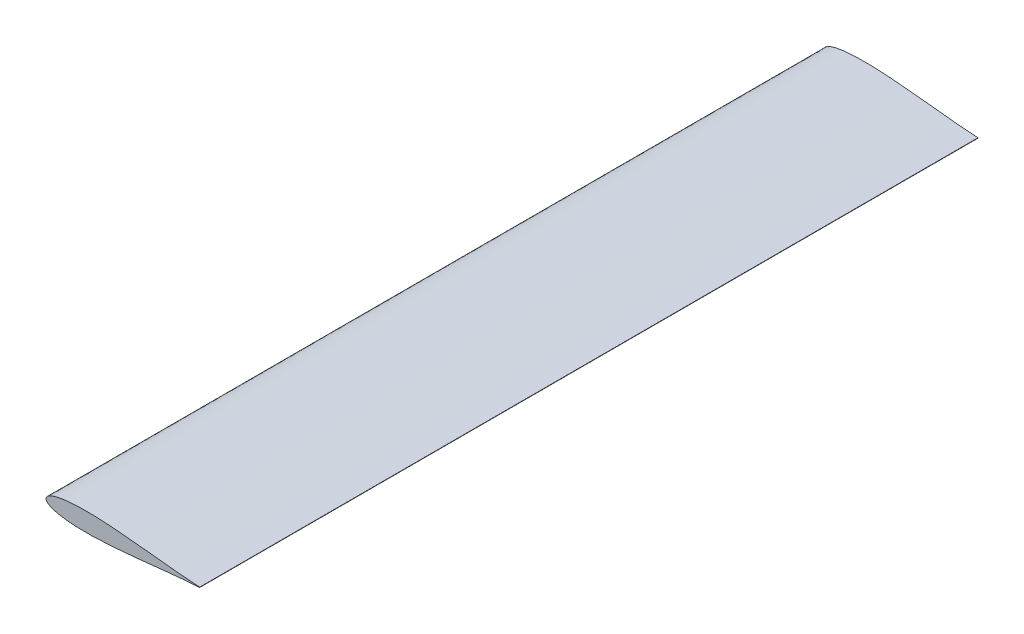
SolidWorks part; units mm, degrees
other "Markup1"
sketch "Sketch3" plane through (-0.0553, -7.355, 609.6) normal (0, 0, 1) x (1, 0, 0)
ref_plane "Front Plane" through (0, 0, 0) normal (0, 0, 1) x (1, 0, 0)
ref_plane "Top Plane" through (0, 0, 0) normal (0, 1, 0) x (1, 0, 0)
ref_plane "Right Plane" through (0, 0, 0) normal (1, 0, 0) x (0, 0, -1)
curve "Curve1"
  spline degree 3 poles (25.3337, -0.0003, 0) (25.4166, 0, 0) (25.3337, 0.0003, 0) (25.2654, 0.0018, 0) (25.098, 0.0055, 0) (24.8899, 0.0127, 0) (24.614, 0.0243, 0) (24.2833, 0.0411, 0) (23.8951, 0.064, 0) (23.4526, 0.0935, 0) (22.9577, 0.1302, 0) (22.4128, 0.1742, 0) (21.8206, 0.2257, 0) (21.184, 0.2845, 0) (20.5061, 0.3502, 0) (19.7901, 0.4224, 0) (19.0396, 0.5004, 0) (18.2582, 0.5832, 0) (17.4498, 0.6697, 0) (16.6182, 0.7589, 0) (15.7675, 0.8494, 0) (14.9019, 0.9396, 0) (14.0255, 1.0282, 0) (13.1427, 1.1135, 0) (12.2578, 1.1941, 0) (11.3749, 1.2683, 0) (10.4986, 1.3345, 0) (9.6329, 1.3915, 0) (8.7821, 1.4377, 0) (7.9504, 1.4721, 0) (7.1418, 1.4935, 0) (6.3603, 1.501, 0) (5.6096, 1.4941, 0) (4.8934, 1.4721, 0) (4.2152, 1.4349, 0) (3.5783, 1.3824, 0) (2.9857, 1.3149, 0) (2.4403, 1.233, 0) (1.9447, 1.1371, 0) (1.5013, 1.0283, 0) (1.1121, 0.9078, 0) (0.7787, 0.7769, 0) (0.5025, 0.6369, 0) (0.2843, 0.4891, 0) (0.1244, 0.334, 0) (0.024, 0.1711, 0) (-0.0113, 0, 0) (0.024, -0.1711, 0) (0.1244, -0.334, 0) (0.2843, -0.4891, 0) (0.5025, -0.6369, 0) (0.7787, -0.7769, 0) (1.1121, -0.9078, 0) (1.5013, -1.0283, 0) (1.9447, -1.1371, 0) (2.4403, -1.233, 0) (2.9857, -1.3149, 0) (3.5783, -1.3824, 0) (4.2152, -1.4349, 0) (4.8934, -1.4721, 0) (5.6096, -1.4941, 0) (6.3603, -1.501, 0) (7.1418, -1.4935, 0) (7.9504, -1.4721, 0) (8.7821, -1.4377, 0) (9.6329, -1.3915, 0) (10.4986, -1.3345, 0) (11.3749, -1.2683, 0) (12.2578, -1.1941, 0) (13.1427, -1.1135, 0) (14.0255, -1.0282, 0) (14.9019, -0.9396, 0) (15.7675, -0.8494, 0) (16.6182, -0.7589, 0) (17.4498, -0.6697, 0) (18.2582, -0.5832, 0) (19.0396, -0.5004, 0) (19.7901, -0.4224, 0) (20.5061, -0.3502, 0) (21.184, -0.2845, 0) (21.8206, -0.2257, 0) (22.4128, -0.1742, 0) (22.9577, -0.1302, 0) (23.4526, -0.0935, 0) (23.8951, -0.064, 0) (24.2833, -0.0411, 0) (24.614, -0.0243, 0) (24.8899, -0.0127, 0) (25.098, -0.0055, 0) (25.2654, -0.0018, 0) (25.3337, -0.0003, 0) (25.4166, 0, 0) (25.3337, 0.0003, 0) knots -0.005355 -0.002385 -0.000597 0 0.000597 0.002385 0.005355 0.009495 0.014784 0.021198 0.028708 0.037278 0.046868 0.05743 0.068917 0.081271 0.094432 0.108338 0.122919 0.138103 0.153815 0.169978 0.186509 0.203327 0.220349 0.237488 0.25466 0.271779 0.288763 0.305527 0.32199 0.338073 0.353702 0.368803 0.383306 0.397149 0.410269 0.422614 0.434133 0.444783 0.454527 0.463337 0.471194 0.478092 0.484042 0.489082 0.493295 0.496842 0.5 0.503158 0.506705 0.510918 0.515958 0.521908 0.528806 0.536663 0.545473 0.555218 0.565867 0.577386 0.589731 0.602851 0.616694 0.631197 0.646298 0.661927 0.67801 0.694473 0.711237 0.728221 0.74534 0.762512 0.779651 0.796673 0.813491 0.830023 0.846185 0.861897 0.877081 0.891662 0.905568 0.918729 0.931083 0.94257 0.953133 0.962722 0.971292 0.978802 0.985216 0.990505 0.994645 0.997615 0.999403 1 1.000597 1.002385 1.005355 periodic
sketch "Sketch2" plane through (0, 0, 0) normal (0, 0, 1) x (1, 0, 0)
  line L0 (0, 0) -> (25.4, 0) construction
  line L1 (0, 0) -> (124.46, 0) construction
  line L2 (120.381, 0.1319) -> (120.381, -0.1319)
  line L3 (62.23, 0) -> (62.23, 5.6527) construction
  spline S0 degree 3 poles (25.3337, -0.0003) (25.4166, 0) (25.3337, 0.0003) (25.2654, 0.0018) (25.098, 0.0055) (24.8899, 0.0127) (24.614, 0.0243) (24.2833, 0.0411) (23.8951, 0.064) (23.4526, 0.0935) (22.9577, 0.1302) (22.4128, 0.1742) (21.8206, 0.2257) (21.184, 0.2845) (20.5061, 0.3502) (19.7901, 0.4224) (19.0396, 0.5004) (18.2582, 0.5832) (17.4498, 0.6697) (16.6182, 0.7589) (15.7675, 0.8494) (14.9019, 0.9396) (14.0255, 1.0282) (13.1427, 1.1135) (12.2578, 1.1941) (11.3749, 1.2683) (10.4986, 1.3345) (9.6329, 1.3915) (8.7821, 1.4377) (7.9504, 1.4721) (7.1418, 1.4935) (6.3603, 1.501) (5.6096, 1.4941) (4.8934, 1.4721) (4.2152, 1.4349) (3.5783, 1.3824) (2.9857, 1.3149) (2.4403, 1.233) (1.9447, 1.1371) (1.5013, 1.0283) (1.1121, 0.9078) (0.7787, 0.7769) (0.5025, 0.6369) (0.2843, 0.4891) (0.1244, 0.334) (0.024, 0.1711) (-0.0113, 0) (0.024, -0.1711) (0.1244, -0.334) (0.2843, -0.4891) (0.5025, -0.6369) (0.7787, -0.7769) (1.1121, -0.9078) (1.5013, -1.0283) (1.9447, -1.1371) (2.4403, -1.233) (2.9857, -1.3149) (3.5783, -1.3824) (4.2152, -1.4349) (4.8934, -1.4721) (5.6096, -1.4941) (6.3603, -1.501) (7.1418, -1.4935) (7.9504, -1.4721) (8.7821, -1.4377) (9.6329, -1.3915) (10.4986, -1.3345) (11.3749, -1.2683) (12.2578, -1.1941) (13.1427, -1.1135) (14.0255, -1.0282) (14.9019, -0.9396) (15.7675, -0.8494) (16.6182, -0.7589) (17.4498, -0.6697) (18.2582, -0.5832) (19.0396, -0.5004) (19.7901, -0.4224) (20.5061, -0.3502) (21.184, -0.2845) (21.8206, -0.2257) (22.4128, -0.1742) (22.9577, -0.1302) (23.4526, -0.0935) (23.8951, -0.064) (24.2833, -0.0411) (24.614, -0.0243) (24.8899, -0.0127) (25.098, -0.0055) (25.2654, -0.0018) (25.3337, -0.0003) (25.4166, 0) (25.3337, 0.0003) knots -0.005355 -0.002385 -0.000597 0 0.000597 0.002385 0.005355 0.009495 0.014784 0.021198 0.028708 0.037278 0.046868 0.05743 0.068917 0.081271 0.094432 0.108338 0.122919 0.138103 0.153815 0.169978 0.186509 0.203327 0.220349 0.237488 0.25466 0.271779 0.288763 0.305527 0.32199 0.338073 0.353702 0.368803 0.383306 0.397149 0.410269 0.422614 0.434133 0.444783 0.454527 0.463337 0.471194 0.478092 0.484042 0.489082 0.493295 0.496842 0.5 0.503158 0.506705 0.510918 0.515958 0.521908 0.528806 0.536663 0.545473 0.555218 0.565867 0.577386 0.589731 0.602851 0.616694 0.631197 0.646298 0.661927 0.67801 0.694473 0.711237 0.728221 0.74534 0.762512 0.779651 0.796673 0.813491 0.830023 0.846185 0.861897 0.877081 0.891662 0.905568 0.918729 0.931083 0.94257 0.953133 0.962722 0.971292 0.978802 0.985216 0.990505 0.994645 0.997615 0.999403 1 1.000597 1.002385 1.005355 only from (25.4, 0) to (25.4, 0) construction
  spline S1 degree 3 poles (25.3337, -0.0003) (25.4166, 0) (25.3337, 0.0003) (25.2654, 0.0018) (25.098, 0.0055) (24.8899, 0.0127) (24.614, 0.0243) (24.2833, 0.0411) (23.8951, 0.064) (23.4526, 0.0935) (22.9577, 0.1302) (22.4128, 0.1742) (21.8206, 0.2257) (21.184, 0.2845) (20.5061, 0.3502) (19.7901, 0.4224) (19.0396, 0.5004) (18.2582, 0.5832) (17.4498, 0.6697) (16.6182, 0.7589) (15.7675, 0.8494) (14.9019, 0.9396) (14.0255, 1.0282) (13.1427, 1.1135) (12.2578, 1.1941) (11.3749, 1.2683) (10.4986, 1.3345) (9.6329, 1.3915) (8.7821, 1.4377) (7.9504, 1.4721) (7.1418, 1.4935) (6.3603, 1.501) (5.6096, 1.4941) (4.8934, 1.4721) (4.2152, 1.4349) (3.5783, 1.3824) (2.9857, 1.3149) (2.4403, 1.233) (1.9447, 1.1371) (1.5013, 1.0283) (1.1121, 0.9078) (0.7787, 0.7769) (0.5025, 0.6369) (0.2843, 0.4891) (0.1244, 0.334) (0.024, 0.1711) (-0.0113, 0) (0.024, -0.1711) (0.1244, -0.334) (0.2843, -0.4891) (0.5025, -0.6369) (0.7787, -0.7769) (1.1121, -0.9078) (1.5013, -1.0283) (1.9447, -1.1371) (2.4403, -1.233) (2.9857, -1.3149) (3.5783, -1.3824) (4.2152, -1.4349) (4.8934, -1.4721) (5.6096, -1.4941) (6.3603, -1.501) (7.1418, -1.4935) (7.9504, -1.4721) (8.7821, -1.4377) (9.6329, -1.3915) (10.4986, -1.3345) (11.3749, -1.2683) (12.2578, -1.1941) (13.1427, -1.1135) (14.0255, -1.0282) (14.9019, -0.9396) (15.7675, -0.8494) (16.6182, -0.7589) (17.4498, -0.6697) (18.2582, -0.5832) (19.0396, -0.5004) (19.7901, -0.4224) (20.5061, -0.3502) (21.184, -0.2845) (21.8206, -0.2257) (22.4128, -0.1742) (22.9577, -0.1302) (23.4526, -0.0935) (23.8951, -0.064) (24.2833, -0.0411) (24.614, -0.0243) (24.8899, -0.0127) (25.098, -0.0055) (25.2654, -0.0018) (25.3337, -0.0003) (25.4166, 0) (25.3337, 0.0003) knots -0.005355 -0.002385 -0.000597 0 0.000597 0.002385 0.005355 0.009495 0.014784 0.021198 0.028708 0.037278 0.046868 0.05743 0.068917 0.081271 0.094432 0.108338 0.122919 0.138103 0.153815 0.169978 0.186509 0.203327 0.220349 0.237488 0.25466 0.271779 0.288763 0.305527 0.32199 0.338073 0.353702 0.368803 0.383306 0.397149 0.410269 0.422614 0.434133 0.444783 0.454527 0.463337 0.471194 0.478092 0.484042 0.489082 0.493295 0.496842 0.5 0.503158 0.506705 0.510918 0.515958 0.521908 0.528806 0.536663 0.545473 0.555218 0.565867 0.577386 0.589731 0.602851 0.616694 0.631197 0.646298 0.661927 0.67801 0.694473 0.711237 0.728221 0.74534 0.762512 0.779651 0.796673 0.813491 0.830023 0.846185 0.861897 0.877081 0.891662 0.905568 0.918729 0.931083 0.94257 0.953133 0.962722 0.971292 0.978802 0.985216 0.990505 0.994645 0.997615 0.999403 1 1.000597 1.002385 1.005355 only from (25.4, 0) to (25.4, 0) construction
  spline S2 degree 3 poles (120.381, 0.1319) (119.9463, 0.1527) (118.8798, 0.2078) (117.0858, 0.3137) (114.9178, 0.4584) (112.4927, 0.6382) (109.8228, 0.8537) (106.9211, 1.106) (103.8017, 1.394) (100.4797, 1.7159) (96.9715, 2.0698) (93.294, 2.4518) (89.4653, 2.8575) (85.5038, 3.2818) (81.4291, 3.7187) (77.2608, 4.162) (73.0193, 4.6041) (68.7252, 5.0383) (64.3994, 5.4564) (60.0631, 5.8512) (55.7372, 6.2145) (51.4429, 6.5392) (47.2011, 6.8181) (43.0324, 7.0448) (38.9571, 7.2131) (34.9951, 7.3181) (31.1655, 7.355) (27.4872, 7.3209) (23.9779, 7.2133) (20.6546, 7.0309) (17.5336, 6.7739) (14.6298, 6.4432) (11.9574, 6.0415) (9.5291, 5.5718) (7.3563, 5.0389) (5.4492, 4.4484) (3.8158, 3.8067) (2.4624, 3.1207) (1.3928, 2.3964) (0.6096, 1.6368) (0.1174, 0.8384) (-0.0553, 0) (0.1174, -0.8384) (0.6096, -1.6368) (1.3928, -2.3964) (2.4624, -3.1207) (3.8158, -3.8067) (5.4492, -4.4484) (7.3563, -5.0389) (9.5291, -5.5718) (11.9574, -6.0415) (14.6299, -6.4433) (17.5336, -6.7739) (20.6546, -7.0309) (23.9779, -7.2133) (27.4872, -7.3209) (31.1655, -7.355) (34.9951, -7.3181) (38.9571, -7.2131) (43.0324, -7.0448) (47.2011, -6.8181) (51.4429, -6.5392) (55.7372, -6.2145) (60.0631, -5.8512) (64.3994, -5.4564) (68.7252, -5.0383) (73.0193, -4.6041) (77.2608, -4.162) (81.4291, -3.7187) (85.5039, -3.2817) (89.4653, -2.8575) (93.294, -2.4518) (96.9715, -2.0698) (100.4797, -1.7159) (103.8017, -1.394) (106.9211, -1.106) (109.8228, -0.8537) (112.4927, -0.6382) (114.9179, -0.4584) (117.0858, -0.3137) (118.8798, -0.2078) (119.9463, -0.1527) (120.381, -0.1319) knots 0.016066 0.016066 0.016066 0.016066 0.021198 0.028708 0.037278 0.046868 0.05743 0.068917 0.081271 0.094432 0.108338 0.122919 0.138103 0.153815 0.169978 0.186509 0.203327 0.220349 0.237488 0.25466 0.271779 0.288763 0.305527 0.32199 0.338073 0.353702 0.368803 0.383306 0.397149 0.410269 0.422614 0.434133 0.444783 0.454527 0.463337 0.471194 0.478092 0.484042 0.489082 0.493295 0.496842 0.5 0.503158 0.506705 0.510918 0.515958 0.521908 0.528806 0.536663 0.545473 0.555218 0.565867 0.577386 0.589731 0.602851 0.616694 0.631197 0.646298 0.661927 0.67801 0.694473 0.711237 0.728221 0.74534 0.762512 0.779651 0.796673 0.813491 0.830023 0.846185 0.861897 0.877081 0.891662 0.905568 0.918729 0.931083 0.94257 0.953133 0.962722 0.971292 0.978802 0.983934 0.983934 0.983934 0.983934
  point P8 (0, 0)
  point P9 (0, 0)
  dimension "D1" = 124.46
  dimension "D2" = 4.079
  dimension "D3" = 5.6527
extrude "Boss-Extrude4" add sketch "Sketch2" along normal blind 609.6
